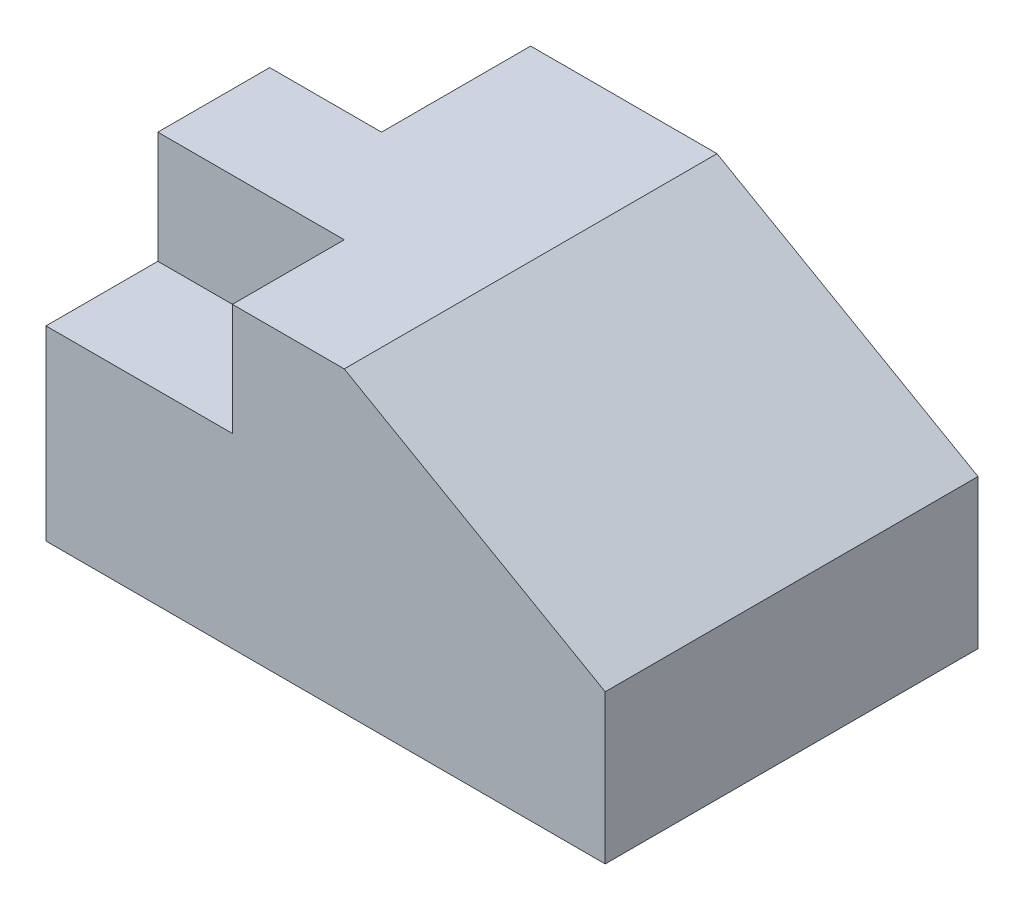
SolidWorks part; units mm, degrees
ref_plane "Front Plane" through (0, 0, 0) normal (0, 0, 1) x (1, 0, 0)
ref_plane "Top Plane" through (0, 0, 0) normal (0, 1, 0) x (1, 0, 0)
ref_plane "Right Plane" through (0, 0, 0) normal (1, 0, 0) x (0, 0, -1)
sketch "Sketch1" plane through (0, 0, 0) normal (0, 0, 1) x (1, 0, 0)
  line L0 (-75, 40) -> (5, 40)
  line L1 (75, 0) -> (75, -40)
  line L2 (75, -40) -> (-75, -40)
  line L3 (-75, -40) -> (-75, 40)
  line L4 (5, 40) -> (75, 0)
  line L5 (-75, 40) -> (-25, 40)
  line L6 (-25, 40) -> (-25, 10)
  line L7 (-25, 10) -> (-75, 10)
  line L8 (-75, 10) -> (-75, 40)
  point P1 (75, 40)
  dimension "D1" = 75
  dimension "D2" = 40
  dimension "D3" = 150
  dimension "D4" = 80
  dimension "D5" = 70
  dimension "D6" = 40
  dimension "D7" = 50
  dimension "D8" = 30
extrude "Boss-Extrude1" add sketch "Sketch1" against normal blind 100 contours L7 L6 L0 L3 | L6 L7 L3 L2 L1 L4 L0 region at (-50, 25, 0) region at (0.293, -8.2234, 0)
extrude "Cut-Extrude1" cut sketch "Sketch1<3>" against normal blind 30 contours L7 L6 L0 L3 region at (-50, 25, 0)
sketch "Sketch1<3>" plane through (0, 0, 0) normal (0, 0, 1) x (1, 0, 0) same geometry as "Sketch1"
sketch "Sketch3" plane through (0, 40, 0) normal (0, 1, 0) x (1, 0, 0)
  line L0 (-75, 100) -> (-75, 60)
  line L1 (-75, 100) -> (-75, 30) construction
  line L2 (-75, 60) -> (-45, 60)
  line L3 (-45, 60) -> (-45, 100)
  line L4 (-75, 100) -> (5, 100) construction
  line L5 (-45, 100) -> (-75, 100)
  dimension "D1" = 50
  dimension "D2" = 40
extrude "Cut-Extrude2" cut sketch "Sketch3" against normal blind 30
